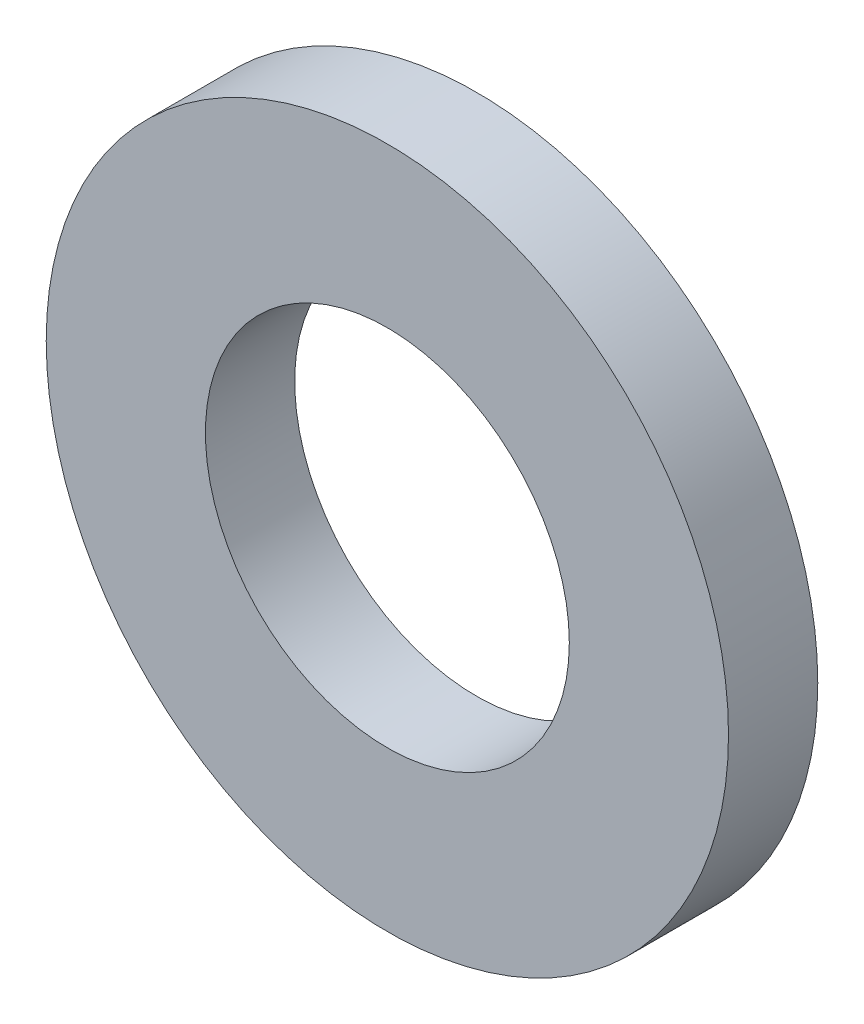
SolidWorks part; units mm, degrees
ref_plane "Front Plane" through (0, 0, 0) normal (0, 0, 1) x (1, 0, 0)
ref_plane "Top Plane" through (0, 0, 0) normal (0, 1, 0) x (1, 0, 0)
ref_plane "Right Plane" through (0, 0, 0) normal (1, 0, 0) x (0, 0, -1)
sketch "Sketch1" plane through (0, 0, 0) normal (0, 0, 1) x (1, 0, 0)
  circle A0 centre (0, 0) radius 3.2 construction
  circle A1 centre (0, 0) radius 6 construction
  point P4 (0, -3.2)
  dimension "ID" = 6.4
  dimension "OD" = 12
sketch "Sketch2" plane through (0, 0, 0) normal (1, 0, 0) x (0, 0, -1)
  line L0 (0, -6) -> (1.57, -6) construction
  dimension "Thickness" = 1.57
sketch "Sketch3" plane through (0, 0, 0) normal (0, 0, 1) x (1, 0, 0)
  circle A0 centre (0, 0) radius 6 construction
  circle A1 centre (0, 0) radius 6
  circle A2 centre (0, 0) radius 3.2 construction
  circle A3 centre (0, 0) radius 3.2
extrude "Boss-Extrude1" add sketch "Sketch3" against normal blind 1.57
ref_axis "Center Axis 1" through (0, 0, -1.6485) along (0, 0, 1)
equation "\"D1@Boss-Extrude1\"=\"Thickness@Sketch2\""
